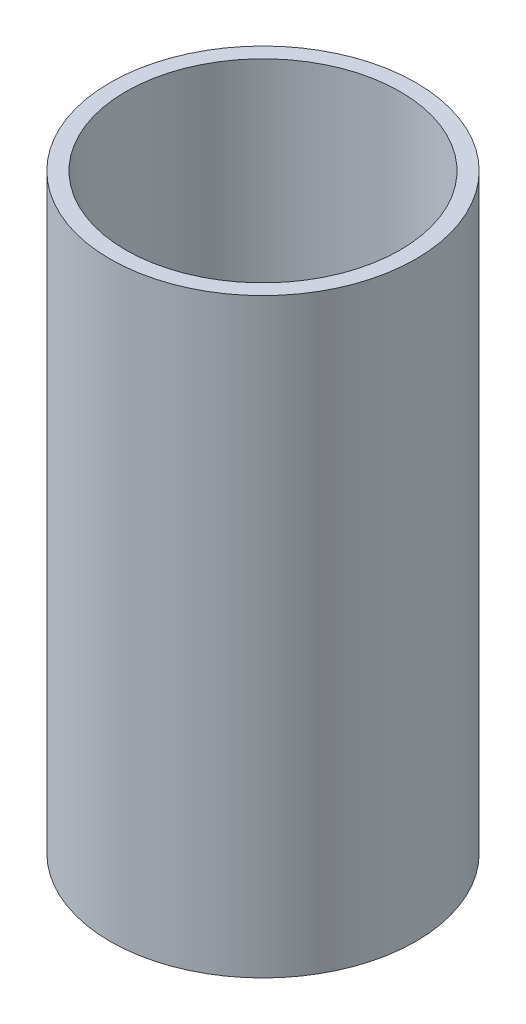
SolidWorks part; units mm, degrees
ref_plane "Front Plane" through (0, 0, 0) normal (0, 0, 1) x (1, 0, 0)
ref_plane "Top Plane" through (0, 0, 0) normal (0, 1, 0) x (1, 0, 0)
ref_plane "Right Plane" through (0, 0, 0) normal (1, 0, 0) x (0, 0, -1)
sketch "Sketch1" plane through (0, 0, 0) normal (0, 1, 0) x (1, 0, 0)
  circle A0 centre (0, 0) radius 42.5
  dimension "SLEEVE_OD" = 85
extrude "Boss-Extrude1" add sketch "Sketch1" along normal blind 164.295
sketch "Sketch2" plane through (0, 0, 0) normal (0, 1, 0) x (1, 0, 0)
  circle A0 centre (0, 0) radius 38.1472
  dimension "BORE_D" = 76.2944
extrude "Cut-Extrude1" cut sketch "Sketch2" along normal through all
chamfer "Chamfer1" distance 2.238 angle 52.292 rebuild error yes
